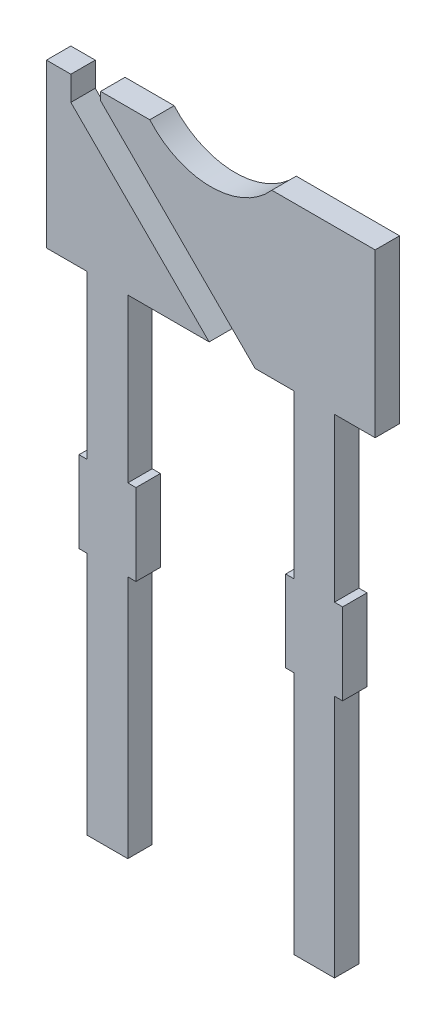
SolidWorks part; units mm, degrees
ref_plane "Front Plane" through (0, 0, 0) normal (0, 0, 1) x (1, 0, 0)
ref_plane "Top Plane" through (0, 0, 0) normal (0, 1, 0) x (1, 0, 0)
ref_plane "Right Plane" through (0, 0, 0) normal (1, 0, 0) x (0, 0, -1)
sketch "Sketch1" plane through (0, 0, 0) normal (0, 0, 1) x (1, 0, 0)
  line L0 (0, -507.9946) -> (0, 24891.7341) construction
  line L1 (-1.27, -1.4316) -> (-1.27, -0.8039) construction
  line L2 (1.27, -1.4316) -> (1.27, -0.8039) construction
  line L3 (1.02, 1.5684) -> (1.02, -1.4316)
  line L4 (1.02, -1.4316) -> (1.52, -1.4316)
  line L5 (1.52, 1.5684) -> (1.52, -1.4316)
  line L6 (-1.52, 1.5684) -> (-1.62, 1.5684)
  line L7 (-1.02, 1.5684) -> (-1.02, -1.4316)
  line L8 (-1.02, -1.4316) -> (-1.52, -1.4316)
  line L9 (-1.52, 1.5684) -> (-1.52, -1.4316)
  line L10 (-1.52, 1.5684) -> (-1.02, 1.5684) construction
  line L11 (-1.02, 1.5684) -> (1.02, 1.5684) construction
  line L12 (1.02, 1.5684) -> (1.52, 1.5684) construction
  line L13 (-1.62, 1.5684) -> (-1.62, 2.5684)
  line L14 (-1.62, 2.5684) -> (-1.52, 2.5684)
  line L15 (-1.02, 1.5684) -> (-0.92, 1.5684)
  line L16 (-0.92, 1.5684) -> (-0.92, 2.5684)
  line L17 (-0.92, 2.5684) -> (-1.02, 2.5684)
  line L18 (1.02, 1.5684) -> (0.92, 1.5684)
  line L19 (0.92, 1.5684) -> (0.92, 2.5684)
  line L20 (0.92, 2.5684) -> (1.02, 2.5684)
  line L21 (1.52, 1.5684) -> (1.62, 1.5684)
  line L22 (1.62, 1.5684) -> (1.62, 2.5684)
  line L23 (1.62, 2.5684) -> (1.52, 2.5684)
  line L24 (-1.52, 2.5684) -> (-1.52, 4.5684)
  line L25 (-1.02, 2.5684) -> (-1.02, 4.5684)
  line L26 (1.02, 4.5684) -> (0.5457, 4.5684)
  line L27 (1.02, 2.5684) -> (1.02, 4.5684)
  line L28 (1.52, 2.5684) -> (1.52, 4.5684)
  line L29 (-1.3543, 6.4684) -> (-1.3543, 6.5684)
  line L30 (-1.3543, 6.5684) -> (2.02, 6.5684)
  line L31 (2.02, 6.5684) -> (2.02, 4.5684)
  line L32 (2.02, 4.5684) -> (1.52, 4.5684)
  line L33 (-1.02, 4.5684) -> (-0.02, 4.5684)
  line L34 (-0.02, 4.5684) -> (-1.72, 6.2684)
  line L35 (-1.72, 6.2684) -> (-1.72, 6.5684)
  line L36 (-1.72, 6.5684) -> (-2.02, 6.5684)
  line L37 (-2.02, 6.5684) -> (-2.02, 4.5684)
  line L38 (-2.02, 4.5684) -> (-1.52, 4.5684)
  line L39 (0.5457, 4.5684) -> (-1.3543, 6.4684)
  point P15 (-0.6571, 1.5684)
  point P17 (0, 1.5684)
  dimension "D1" = 2.54
  dimension "D2" = 0.5
  dimension "D3" = 3
  dimension "D4" = 0.7
  dimension "D5" = 6
  dimension "D6" = 1
  dimension "D7" = 2
  dimension "D8" = 45
  dimension "D9" = 0.4
  dimension "D10" = 0.3
  dimension "D11" = 0.1
  dimension "D12" = 0.5
  dimension "D13" = 0.5
  dimension "D14" = 0.3
  dimension "D15" = 2.04
extrude "Boss-Extrude1" add sketch "Sketch1" along normal mid plane 0.3
sketch "Sketch2" plane through (0, 0, 0.15) normal (0, 0, 1) x (1, 0, 0)
  line L0 (0, -1000) -> (0, 49000) construction
  line L1 (2.02, 6.5684) -> (-1.3543, 6.5684) construction
  line L2 (-0.75, 6.5684) -> (0.75, 6.5684)
  arc A0 (-0.75, 6.5684) -> (0.75, 6.5684) centre (0, 7.2299) ccw
  dimension "D2" = 1
  dimension "D1" = 1.5
extrude "Cut-Extrude1" cut sketch "Sketch2" against normal through all
ref_point "focus"
ref_point "Cathode pin"
ref_point "Anode pin"
